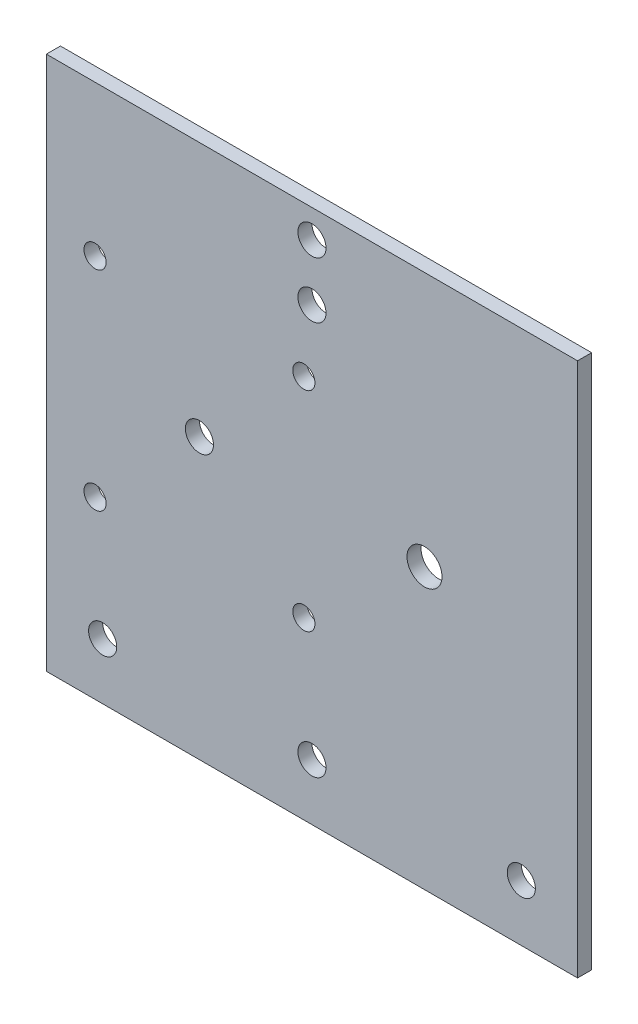
SolidWorks part; units mm, degrees
ref_plane "Front Plane" through (0, 0, 0) normal (0, 0, 1) x (1, 0, 0)
ref_plane "Top Plane" through (0, 0, 0) normal (0, 1, 0) x (1, 0, 0)
ref_plane "Right Plane" through (0, 0, 0) normal (1, 0, 0) x (0, 0, -1)
sketch "Sketch1" plane through (0, 0, 0) normal (0, 0, 1) x (1, 0, 0)
  line L0 (0, 12.7) -> (119.9, 12.7) construction
  line L1 (0, 0) -> (119.9, 0)
  line L2 (0, 0) -> (0, 120.65)
  line L3 (0, 120.65) -> (119.9, 120.65)
  line L4 (119.9, 0) -> (119.9, 120.65)
  line L5 (0, 25.4) -> (119.9, 25.4) construction
  line L6 (59.95, 120.65) -> (59.95, 0) construction
  line L7 (34.55, 91.325) -> (34.55, 34.925) construction
  line L8 (6.35, 34.925) -> (62.75, 34.925) construction
  line L9 (6.35, 34.925) -> (6.35, 91.325) construction
  line L10 (6.35, 91.325) -> (62.75, 91.325) construction
  line L11 (62.75, 34.925) -> (62.75, 91.325) construction
  line L12 (6.35, 63.125) -> (62.75, 63.125) construction
  circle A0 centre (12.7, 12.7) radius 3.175
  circle A1 centre (59.95, 12.7) radius 3.175
  circle A2 centre (107.2, 12.7) radius 3.175
  circle A3 centre (34.55, 63.125) radius 3.175
  circle A4 centre (10.98, 86.695) radius 2.5
  circle A5 centre (58.12, 86.695) radius 2.5
  circle A6 centre (58.12, 39.555) radius 2.5
  circle A7 centre (10.98, 39.555) radius 2.5
  circle A8 centre (85.35, 63.125) radius 3.95
  circle A9 centre (59.95, 114.3) radius 3.175
  circle A10 centre (59.95, 101.6) radius 3.175
  dimension "D5" = 6.35
  dimension "D9" = 5
  dimension "D10" = 6.35
  dimension "D17" = 7.9
  dimension "D20" = 6.35
  dimension "D21" = 12.7
  dimension "D2" = 120.65
  dimension "D3" = 12.7
  dimension "D4" = 25.4
  dimension "D6" = 12.7
  dimension "D7" = 12.7
  dimension "D8" = 56.4
  dimension "D11" = 47.14
  dimension "D12" = 47.14
  dimension "D13" = 47.14
  dimension "D14" = 47.14
  dimension "D15" = 6.35
  dimension "D16" = 9.525
  dimension "D18" = 50.8
  dimension "D19" = 25.4
  dimension "D22" = 6.35
extrude "Boss-Extrude1" add sketch "Sketch1" along normal blind 3.175
